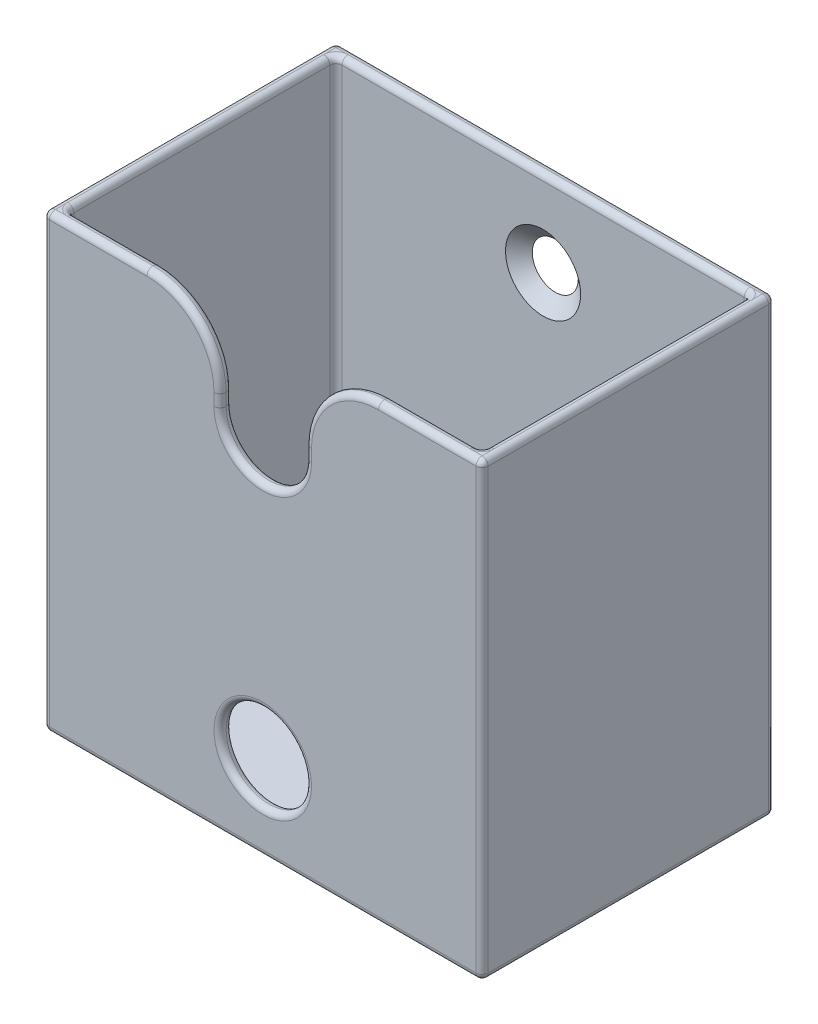
SolidWorks part; units mm, degrees
ref_plane "Front Plane" through (0, 0, 0) normal (0, 0, 1) x (1, 0, 0)
ref_plane "Top Plane" through (0, 0, 0) normal (0, 1, 0) x (1, 0, 0)
ref_plane "Right Plane" through (0, 0, 0) normal (1, 0, 0) x (0, 0, -1)
sketch "Sketch1" plane through (0, 0, 0) normal (0, 1, 0) x (1, 0, 0)
  line L1 (-26.9875, -17.4625) -> (26.9875, -17.4625)
  line L2 (-26.9875, -17.4625) -> (-26.9875, 17.4625)
  line L3 (-26.9875, 17.4625) -> (26.9875, 17.4625)
  line L4 (26.9875, -17.4625) -> (26.9875, 17.4625)
  line L5 (-26.9875, -17.4625) -> (26.9875, 17.4625) construction
  line L6 (-26.9875, 17.4625) -> (26.9875, -17.4625) construction
  point P0 (0, 0)
  dimension "D1" = 53.975
  dimension "D2" = 34.925
extrude "Extrude-Thin1" add sketch "Sketch1" along normal mid plane 57.15 thin thin type one direction wall 1.5875
sketch "Sketch2" plane through (0, -28.575, 0) normal (0, -1, 0) x (1, 0, 0)
  line L4 (28.575, -19.05) -> (28.575, 19.05)
  line L5 (28.575, 19.05) -> (-28.575, 19.05)
  line L6 (-28.575, 19.05) -> (-28.575, -19.05)
  line L7 (-28.575, -19.05) -> (28.575, -19.05)
  line L8 (28.575, -19.05) -> (28.575, 19.05)
  line L9 (28.575, 19.05) -> (-28.575, 19.05)
  line L10 (-28.575, 19.05) -> (-28.575, -19.05)
  line L11 (-28.575, -19.05) -> (28.575, -19.05)
  dimension "D1" = 0
extrude "Boss-Extrude1" add sketch "Sketch2" along normal blind 1.5875
sketch "Sketch3" plane through (0, 0, 19.05) normal (0, 0, 1) x (1, 0, 0)
  line L0 (0, 28.575) -> (0, 17.4625) construction
  line L1 (-28.575, 28.575) -> (28.575, 28.575) construction
  line L2 (5.5562, 28.575) -> (5.5563, 17.4625)
  line L3 (-5.5562, 28.575) -> (-5.5562, 17.4625)
  line L5 (0, -30.1625) -> (0, -19.05) construction
  line L6 (28.575, -30.1625) -> (-28.575, -30.1625) construction
  line L7 (-26.9875, -28.575) -> (26.9875, -28.575) construction
  arc A0 (5.5562, 28.575) -> (-5.5562, 28.575) centre (0, 28.575) ccw
  arc A1 (-5.5562, 17.4625) -> (5.5563, 17.4625) centre (0, 17.4625) ccw
  circle A2 centre (0, -19.05) radius 5.5563
  point P5 (0, 23.0188)
  dimension "D1" = 11.1125
  dimension "D2" = 9.525
extrude "Cut-Extrude1" cut sketch "Sketch3" against normal up to next
sketch "Sketch4" plane through (0, 0, -17.4625) normal (0, 0, 1) x (1, 0, 0)
  point P0 (0, 17.4625)
  point P1 (0, -19.05)
hole_wizard "CSK for #10 Flat Head Machine Screw (100)1" positions "3DSketch1" profile "Sketch5" countersink size "#10" standard "ANSI Inch" end condition through all
sketch3d "3DSketch1"
  point P0 (0, 17.4625, -17.4625)
  point P3 (0, -19.05, -17.4625)
sketch "Sketch5" plane through (0, 17.4625, -17.4625) normal (1, 0, 0) x (0, -1, 0)
  line L0 (0, 0) -> (0, 1.5875)
  line L1 (0, 1.5875) -> (2.5527, 1.5875)
  line L2 (2.5527, 1.5875) -> (2.5527, 1.9608)
  line L3 (2.5527, 1.9608) -> (4.8895, 0)
  line L5 (4.8895, 0) -> (0, 0)
  line L6 (-2.5527, 1.9608) -> (-4.8895, 0) construction
  line L11 (0, -6.35) -> (0, 107.95) construction
  dimension "Thru Hole Dia." = 5.1054
  dimension "Thru Hole Depth" = 1.5875
  dimension "Near C'Sink Dia." = 9.779
  dimension "Near C'Sink Angle" = 100
fillet "Fillet1" radius 9.525 2 edges at (5.5562, 28.575, 18.2563) (-5.5562, 28.575, 18.2563)
fillet "Fillet4" radius 0.7937 38 edges at (-8.3461, 25.7852, 19.05) (-5.5562, 18.2563, 19.05) (0, 11.9063, 19.05) (5.5563, 18.2563, 19.05) (8.3461, 25.7852, 19.05) (0, -30.1625, 19.05) (0, -30.1625, -19.05) (-28.575, -0.7937, 19.05) (-28.575, -30.1625, 0) (-28.575, -0.7937, -19.05) (28.575, -0.7937, -19.05) (28.575, -30.1625, 0) (28.575, -0.7937, 19.05) (0, 11.9063, 17.4625) (-5.5562, 18.2563, 17.4625) (-8.3461, 25.7852, 17.4625) (-26.9875, 0, 17.4625) (26.9875, 0, 17.4625) (8.3461, 25.7852, 17.4625) (5.5563, 18.2563, 17.4625) (26.9875, 28.575, 0) (0, 28.575, -17.4625) (-26.9875, 28.575, 0) (-21.0344, 28.575, 17.4625) (-21.8281, 28.575, 19.05) (-28.575, 28.575, 0) (0, 28.575, -19.05) (28.575, 28.575, 0) (21.8281, 28.575, 19.05) (21.0344, 28.575, 17.4625) (5.5563, -19.05, 19.05) (-5.5563, -19.05, 17.4625) (-26.9875, -28.575, 0) (0, -28.575, -17.4625) (26.9875, -28.575, 0) (0, -28.575, 17.4625) (26.9875, 0, -17.4625) (-26.9875, 0, -17.4625)
equation "\"wall_thickness\"= 1 / 16"
equation "\"D5@Extrude-Thin1\"=\"wall_thickness\""
equation "\"D1@Boss-Extrude1\"=\"wall_thickness\""
equation "\"D1@Fillet4\"=\"wall_thickness\"/2"
